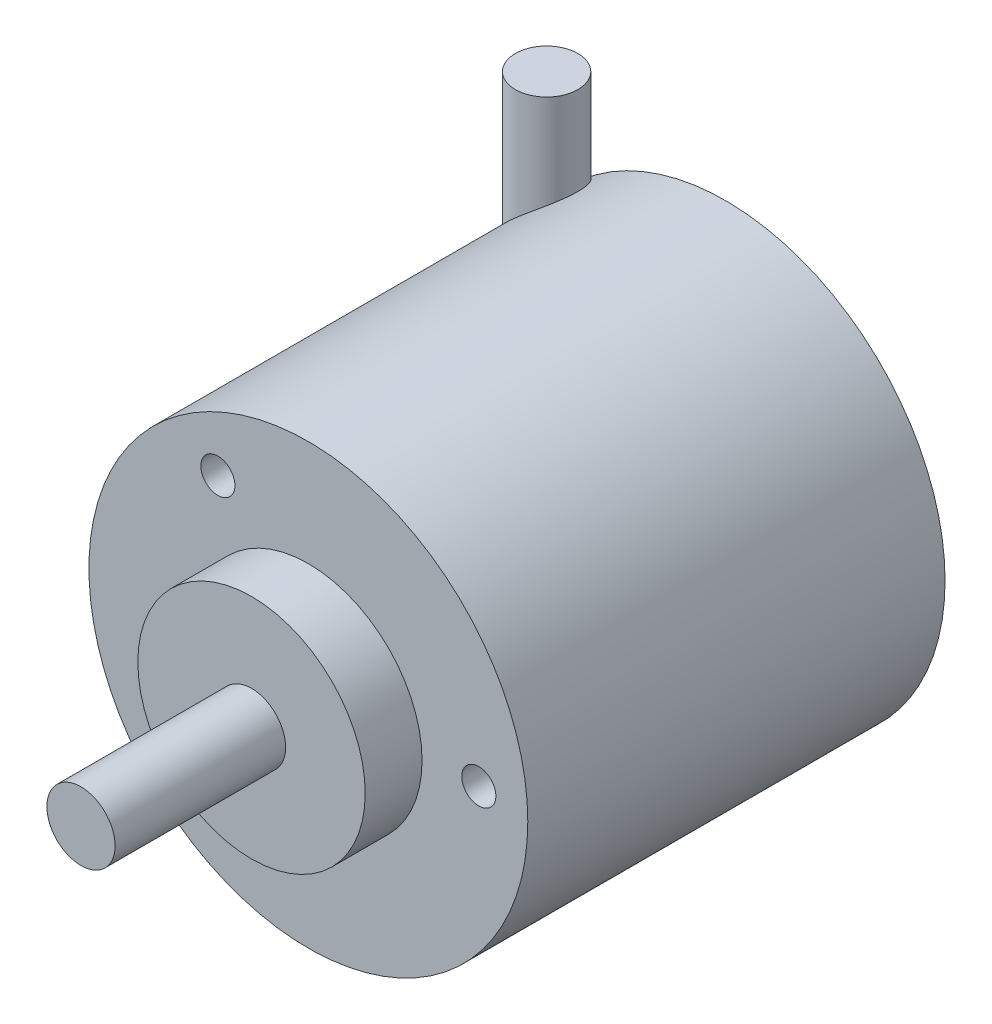
SolidWorks part; units mm, degrees
ref_plane "Front Plane" through (0, 0, 0) normal (0, 0, 1) x (1, 0, 0)
ref_plane "Top Plane" through (0, 0, 0) normal (0, 1, 0) x (1, 0, 0)
ref_plane "Right Plane" through (0, 0, 0) normal (1, 0, 0) x (0, 0, -1)
sketch "Sketch1" plane through (0, 0, 0) normal (0, 0, 1) x (1, 0, 0)
  circle A0 centre (-14.1274, 5.3793) radius 19.3
  dimension "D1" = 38.6
extrude "Boss-Extrude1" add sketch "Sketch1" along normal blind 36.7
sketch "Sketch3" plane through (0, 0, 36.7) normal (0, 0, 1) x (1, 0, 0)
  circle A0 centre (-14.1274, 5.3793) radius 10
  circle A1 centre (-14.1274, 5.3793) radius 19.3 construction
  dimension "D1" = 20
  dimension "D2" = 0
extrude "Boss-Extrude2" add sketch "Sketch3" along normal blind 5
sketch "Sketch4" plane through (0, 0, 41.7) normal (0, 0, 1) x (1, 0, 0)
  circle A0 centre (-14.1274, 5.3793) radius 3
  circle A1 centre (-14.1274, 5.3793) radius 10 construction
  dimension "D1" = 6
  dimension "D2" = 0
extrude "Boss-Extrude3" add sketch "Sketch4" along normal blind 15
sketch "Sketch5" plane through (0, 0, 36.7) normal (0, 0, 1) x (1, 0, 0)
  circle A0 centre (0.863, 5.9165) radius 1.5
  circle A1 centre (-14.1274, 5.3793) radius 3 construction
  circle A2 centre (-21.1574, -7.8714) radius 1.5
  circle A3 centre (-22.0878, 18.0927) radius 1.5
  point P10 (-14.1274, 5.3793)
  dimension "D1" = 3
  dimension "D2" = 15
  dimension "D3" = 3
ref_plane "Plane1" through (0, 24.6793, 0) normal (0, 1, 0) x (1, 0, 0)
sketch "Sketch8" plane through (0, 24.6793, 0) normal (0, 1, 0) x (1, 0, 0)
  circle A0 centre (-26.8321, -3.0426) radius 2.75
  dimension "D1" = 5.5
extrude "Boss-Extrude4" add sketch "Sketch8" against normal blind 15 separate body
sketch "Sketch9" plane through (0, 24.6793, 0) normal (0, 1, 0) x (1, 0, 0)
  circle A0 centre (-26.8321, -3.0426) radius 2.75
extrude "Boss-Extrude5" add sketch "Sketch9" along normal blind 5
extrude "Cut-Extrude1" cut sketch "Sketch5" against normal blind 10
